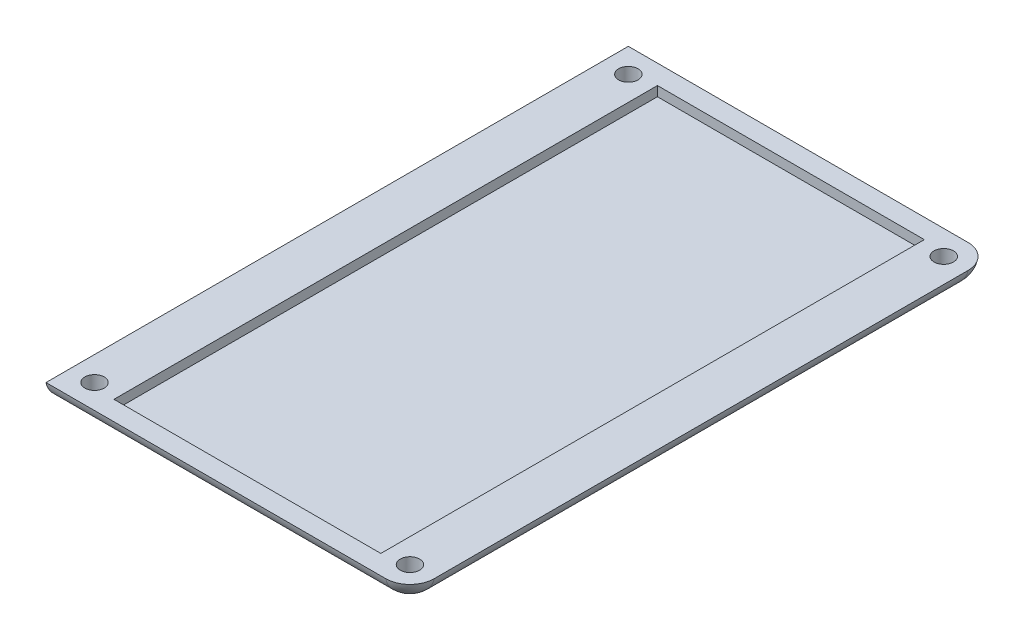
SolidWorks part; units mm, degrees
ref_plane "Front Plane" through (0, 0, 0) normal (0, 0, 1) x (1, 0, 0)
ref_plane "Top Plane" through (0, 0, 0) normal (0, 1, 0) x (1, 0, 0)
ref_plane "Right Plane" through (0, 0, 0) normal (1, 0, 0) x (0, 0, -1)
sketch "Sketch1" plane through (0, 0, 0) normal (0, 1, 0) x (1, 0, 0)
  line L1 (0, 0) -> (37.5, 0)
  line L2 (0, 0) -> (0, 60)
  line L3 (0, 60) -> (37.5, 60)
  line L4 (37.5, 0) -> (37.5, 60)
  dimension "D1" = 60
  dimension "D2" = 37.5
extrude "Boss-Extrude1" add sketch "Sketch1" along normal blind 2
sketch "Sketch2" plane through (0, 2, 0) normal (0, 1, 0) x (1, 0, 0)
  line L0 (0, 60) -> (0, 0) construction
  line L1 (37.5, 60) -> (0, 60) construction
  line L2 (37.5, 0) -> (37.5, 60) construction
  line L3 (0, 0) -> (37.5, 0) construction
  circle A0 centre (2.5, 57.5) radius 1
  circle A1 centre (35, 57.5) radius 1
  circle A2 centre (35, 2.5) radius 1
  circle A3 centre (2.5, 2.5) radius 1
  dimension "D2" = 2
  dimension "D6" = 2
  dimension "D7" = 2
  dimension "D12" = 2
  dimension "D1" = 2.5
  dimension "D3" = 2.5
  dimension "D4" = 2.5
  dimension "D5" = 2.5
  dimension "D8" = 2.5
  dimension "D9" = 2.5
  dimension "D10" = 2.5
  dimension "D11" = 2.5
extrude "Cut-Extrude1" cut sketch "Sketch2" against normal through all
sketch "Sketch3" plane through (0, 2, 0) normal (0, 1, 0) x (1, 0, 0)
  line L0 (37.5, 0) -> (37.5, 60) construction
  line L1 (5, 58) -> (32.5, 58)
  line L2 (5, 58) -> (5, 2)
  line L3 (5, 2) -> (32.5, 2)
  line L4 (32.5, 58) -> (32.5, 2)
  line L5 (0, 60) -> (0, 0) construction
  line L6 (0, 0) -> (37.5, 0) construction
  line L7 (37.5, 60) -> (0, 60) construction
  dimension "D1" = 56
  dimension "D2" = 27.5
  dimension "D3" = 5
  dimension "D4" = 5
  dimension "D5" = 2
  dimension "D6" = 2
extrude "Cut-Extrude2" cut sketch "Sketch3" against normal blind 1
fillet "Fillet1" radius 2.5 2 edges at (37.5, 1, -60) (37.5, 1, 0)
fillet "Fillet2" radius 2.5 5 edges at (36.7678, 0, -59.2678) (17.5, 0, -60) (37.5, 0, -30) (17.5, 0, 0) (36.7678, 0, -0.7322)
